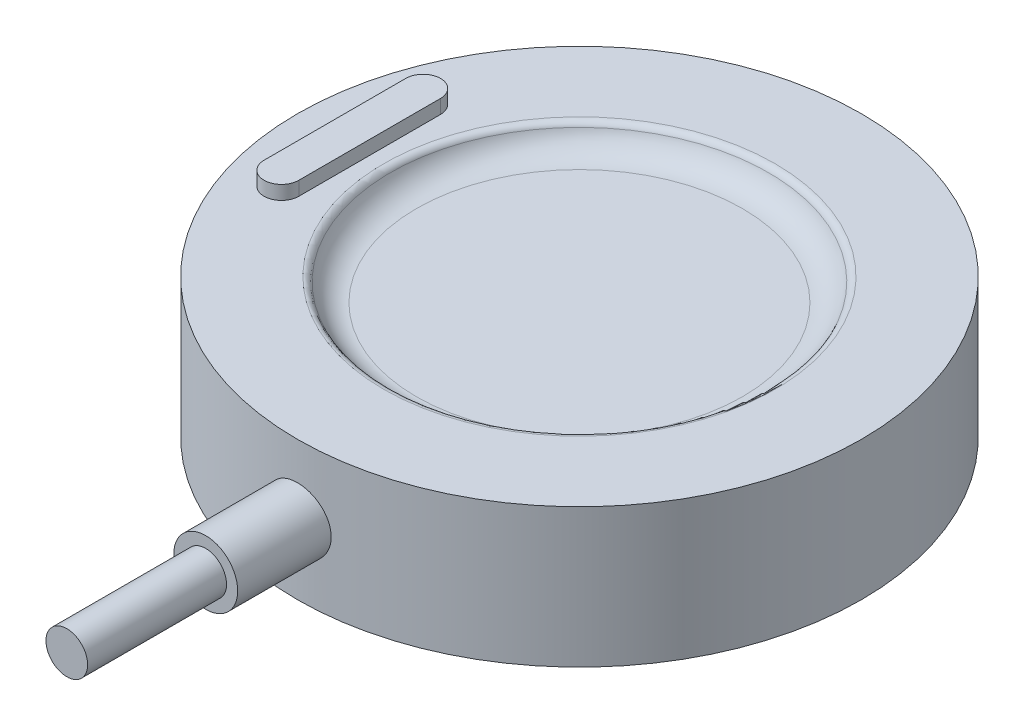
SolidWorks part; units mm, degrees
ref_plane "前视基准面" through (0, 0, 0) normal (0, 0, 1) x (1, 0, 0)
ref_plane "上视基准面" through (0, 0, 0) normal (0, 1, 0) x (1, 0, 0)
ref_plane "右视基准面" through (0, 0, 0) normal (1, 0, 0) x (0, 0, -1)
other "Configuration Table"
sketch "草图1" plane through (0, 0, 0) normal (0, 1, 0) x (1, 0, 0)
  circle A0 centre (0, 0) radius 20.3
  dimension "D1" = 40.6
extrude "凸台-拉伸1" add sketch "草图1" along normal blind 10
sketch "草图2" plane through (0, 0, 0) normal (0, 0, 1) x (1, 0, 0)
  line L0 (0, 10) -> (0, 0) construction
  line L1 (0, 10) -> (0, 0)
  line L2 (20.3, 10) -> (-20.3, 10) construction
  circle A0 centre (0, 5) radius 2.3
  point P9 (0, 10)
  point P10 (0, 0)
  point P11 (0, 0)
  point P12 (0, 0)
  dimension "D1" = 4.6
extrude "凸台-拉伸2" add sketch "草图2" along normal blind 26.9 contours A0
sketch "草图3" plane through (0, 0, 26.9) normal (0, 0, 1) x (1, 0, 0)
  circle A0 centre (0, 5) radius 1.5
  circle A1 centre (0, 5) radius 2.3 construction
  point P3 (0, 0)
  dimension "D1" = 3
extrude "凸台-拉伸3" add sketch "草图3" along normal blind 10
sketch "草图4" plane through (0, 10, 0) normal (0, 1, 0) x (1, 0, 0)
  line L0 (-16.35, 5.1) -> (-16.35, -5.1) construction
  line L3 (-15.1, 5.1) -> (-15.1, -5.1)
  line L4 (-17.6, 5.1) -> (-17.6, -5.1)
  line L5 (-24.779, 6.35) -> (5.2784, 6.35) construction
  line L6 (-28.8111, -6.35) -> (9.0172, -6.35) construction
  line L7 (0, 6.35) -> (0, -6.35) construction
  line L8 (-20.3, 16.534) -> (-20.3, -22.1413) construction
  arc A2 (-15.1, 5.1) -> (-17.6, 5.1) centre (-16.35, 5.1) ccw
  arc A3 (-17.6, -5.1) -> (-15.1, -5.1) centre (-16.35, -5.1) ccw
  circle A4 centre (0, 0) radius 20.3 construction
  point P2 (-16.35, 0)
  dimension "D1" = 2.5
  dimension "D2" = 12.7
  dimension "D3" = 5.2
extrude "凸台-拉伸4" add sketch "草图4" along normal blind 1
sketch "草图5" plane through (0, 10, 0) normal (0, 1, 0) x (1, 0, 0)
  circle A0 centre (0, 0) radius 13.7
  dimension "D1" = 27.4
extrude "切除-拉伸1" cut sketch "草图5" against normal blind 1.63
fillet "圆角1" radius 2 1 edges at (0, 8.37, 13.7)
fillet "圆角2" radius 0.5 1 edges at (0, 10, 13.7)
